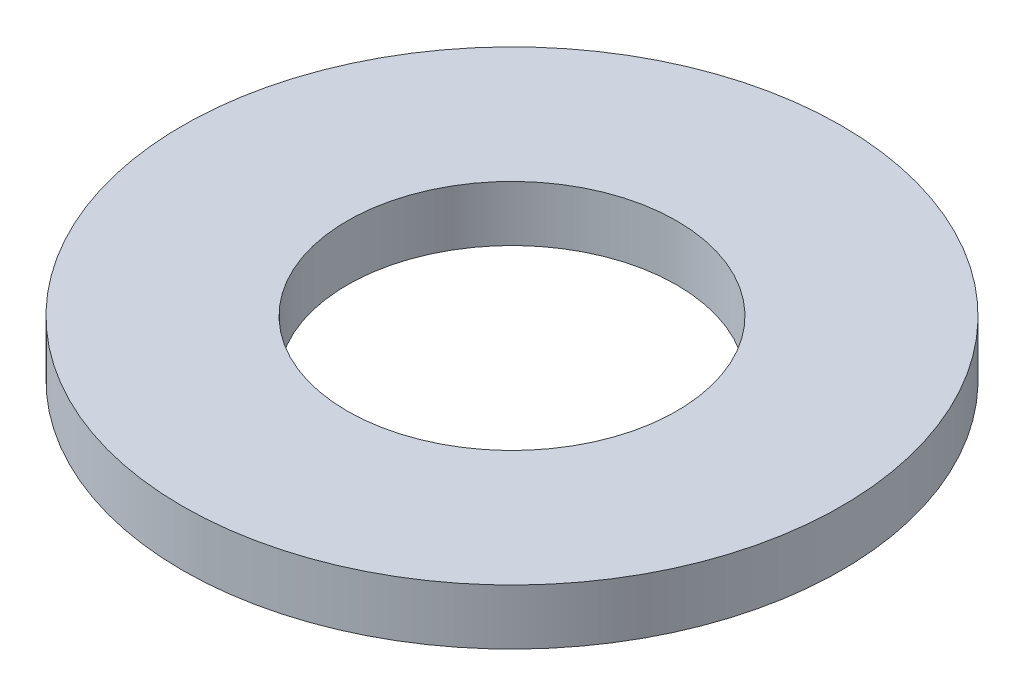
SolidWorks part; units mm, degrees
ref_plane "Front Plane" through (0, 0, 0) normal (0, 0, 1) x (1, 0, 0)
ref_plane "Top Plane" through (0, 0, 0) normal (0, 1, 0) x (1, 0, 0)
ref_plane "Right Plane" through (0, 0, 0) normal (1, 0, 0) x (0, 0, -1)
sketch "Sketch1" plane through (0, 0, 0) normal (0, 1, 0) x (1, 0, 0)
  circle A0 centre (0, 0) radius 95
  dimension "FLANGE_OD" = 190
extrude "Boss-Extrude1" add sketch "Sketch1" along normal blind 16
sketch "Sketch2" plane through (0, 0, 0) normal (0, 1, 0) x (1, 0, 0)
  circle A0 centre (0, 0) radius 47.5
  dimension "BORE_D" = 95
extrude "Cut-Extrude1" cut sketch "Sketch2" along normal through all
sketch "Sketch3" plane through (0, 16, 0) normal (0, 1, 0) x (1, 0, 0)
  circle A0 centre (0, 0) radius 36.2562 construction
  circle A1 centre (-36.2562, 0) radius 6.0963
  dimension "BOLT_D" = 12.1927
  dimension "BOLT_PCD" = 72.5124
extrude "Cut-Extrude2" cut sketch "Sketch3" against normal blind 14.5087 rebuild error yes
pattern_circular "CirPattern1" count 8 over 360 rebuild error yes
